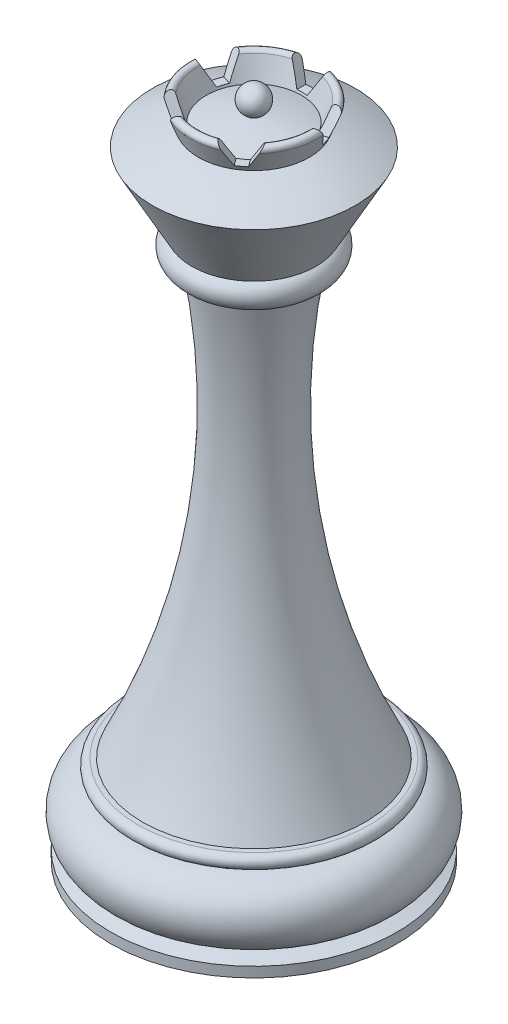
SolidWorks part; units mm, degrees
ref_plane "Front Plane" through (0, 0, 0) normal (0, 0, 1) x (1, 0, 0)
ref_plane "Top Plane" through (0, 0, 0) normal (0, 1, 0) x (1, 0, 0)
ref_plane "Right Plane" through (0, 0, 0) normal (1, 0, 0) x (0, 0, -1)
sketch "Sketch1" plane through (0, 0, 0) normal (0, 0, 1) x (1, 0, 0)
  line L0 (0, 0) -> (0, -19.2438) construction
  line L1 (0, 0) -> (12.5016, 0)
  line L2 (12.4781, -1.4284) -> (12.4781, -1.4919)
  line L3 (0, -9.6219) -> (15.4504, -9.6219)
  line L4 (15.4504, -9.6219) -> (15.4504, -8.5301)
  line L5 (15.4504, -8.5301) -> (13.8939, -8.0177)
  line L6 (0, 0) -> (0, -9.6219)
  line L7 (0, 0) -> (0, 60.2281) construction
  line L8 (0, 54.9102) -> (0, 53.3538) construction
  line L9 (10.9414, 57.0217) -> (6.6894, 49.2108)
  line L10 (0, 60.2281) -> (0, -9.6219)
  line L11 (0, 55.9495) -> (0, 60.2281)
  line L12 (0, 61.9057) -> (0, 60.2281)
  line L13 (5.1217, 59.2856) -> (6.0004, 61.5259)
  line L14 (10.9414, 57.0217) -> (0, 57.0217)
  line L15 (6.8281, 61.2013) -> (5.9791, 59.0367)
  line L16 (0, 62.9009) -> (0, 60.2281)
  arc A0 (12.5016, 0) -> (12.4781, -1.4284) centre (12.5016, -0.7144) cw
  arc A1 (13.8939, -8.0177) -> (12.4781, -1.4919) centre (12.4226, -4.9204) ccw
  arc A3 (6.6894, 49.2108) -> (5.5256, 46.4469) centre (5.9689, 47.8872) cw
  arc A5 (10.9414, 57.0217) -> (0, 60.2281) centre (-2.9096, 30.0279) ccw
  arc A8 (6.0004, 61.5259) -> (6.8281, 61.2013) centre (6.4143, 61.3636) cw
  arc A9 (0.6003, 60.1642) -> (0, 62.9009) centre (0, 61.4668) ccw
  arc A10 (5.5256, 46.4469) -> (11.9974, 0) centre (79.1244, 33.0277) ccw
  point P28 (11.9704, 0)
  point P33 (0, 0)
  point P34 (11.6886, 0)
  point P36 (11.4182, 0)
  point P37 (11.6538, 0)
  point P38 (4.8466, 46.8269)
  point P39 (5.2849, 46.5023)
  point P40 (5.5571, 46.3613)
  point P41 (12.1313, 0)
  point P42 (11.9035, 0)
  point P43 (11.3779, 0)
  point P44 (5.8984, 46.2649)
  point P45 (5.5439, 46.3473)
  point P46 (11.6247, 0)
  point P47 (11.6247, 56.7606)
  point P48 (5.6274, 46.3359)
  point P49 (5.8452, 46.3563)
  point P50 (5.5256, 46.4469)
  point P51 (11.9974, 0)
  point P52 (10.9414, 57.0217)
  dimension "D1" = 0.0635
  dimension "D4" = 0.7144
  dimension "D3" = 3.429
  dimension "D7" = 1.507
  dimension "D2" = 12.5016
  dimension "D5" = 9.6219
  dimension "D6" = 69.85
revolve "Revolve1" add sketch "Sketch1" angle 360 about L0 region at (3.6703, 27.0216, 0) region at (7.4657, -4.9178, 0) region at (6.0451, 60.4283, 0)
sketch "Sketch8" plane through (0, 0, 0) normal (0, 0, 1) x (1, 0, 0)
  line L0 (-0.5549, 59.5182) -> (0.5549, 59.5182)
  line L1 (0, 72.9777) -> (0, -12.7055) construction
  line L2 (-0.5549, 59.5182) -> (-2.0143, 62.222)
  line L3 (-2.0143, 62.222) -> (2.0143, 62.222)
  line L4 (2.0143, 62.222) -> (0.5549, 59.5182)
extrude "Cut-Extrude2" cut sketch "Sketch8" against normal through all
sketch "Sketch5" plane through (0, 0, 0) normal (0, 0, 1) x (1, 0, 0)
  line L0 (0, 68.7531) -> (0, -23.0767) construction
  line L1 (5.9791, 59.0367) -> (-5.9791, 59.0367) construction
  line L2 (6.5766, 61.7775) -> (-6.7034, 61.7775) construction
  line L4 (0.855, 59.0367) -> (-0.855, 59.0367)
  line L5 (-2.1076, 61.7775) -> (-0.855, 59.0367)
  line L6 (-0.855, 59.0367) -> (0.855, 59.0367)
  line L7 (0.855, 59.0367) -> (2.1076, 61.7775)
  line L10 (-2.1076, 61.7775) -> (2.1076, 61.7775)
  arc A0 (6.8281, 61.2013) -> (6.0004, 61.5259) centre (6.4143, 61.3636) ccw construction
pattern_circular "CirPattern2" count 5 over 360 about axis through (0, -9.6219, 0) along (0, 1, 0) of "Cut-Extrude2"
revolve "Revolve3" add sketch "Sketch1<5>" angle 360 about L0 region at (4.0052, 58.2315, 0) region at (0.6177, 61.4976, 0)
sketch "Sketch1<5>" plane through (0, 0, 0) normal (0, 0, 1) x (1, 0, 0) same geometry as "Sketch1"
